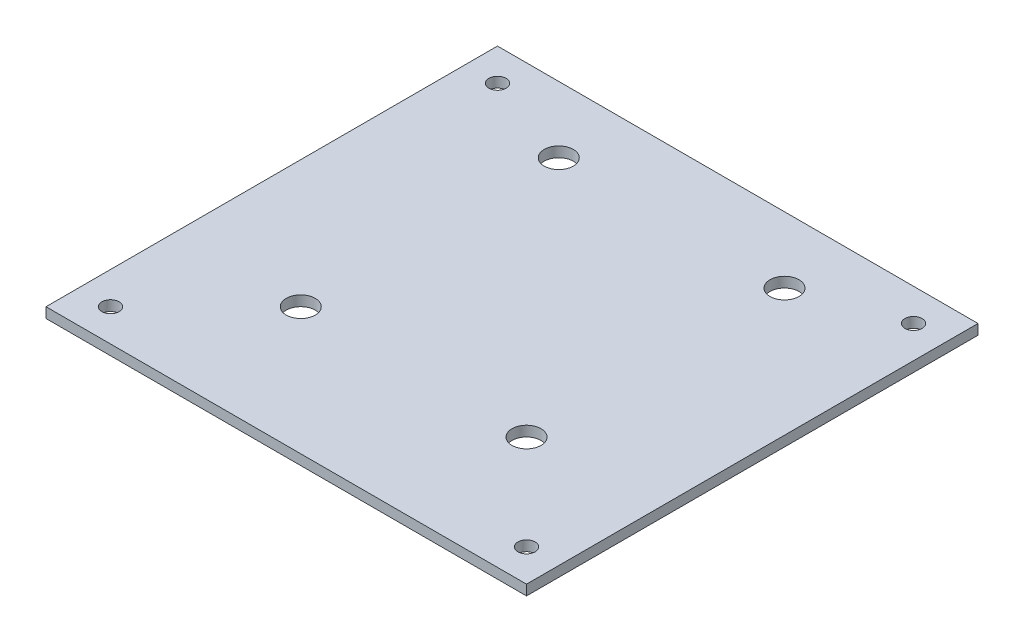
SolidWorks part; units mm, degrees
ref_plane "Front Plane" through (0, 0, 0) normal (0, 0, 1) x (1, 0, 0)
ref_plane "Top Plane" through (0, 0, 0) normal (0, 1, 0) x (1, 0, 0)
ref_plane "Right Plane" through (0, 0, 0) normal (1, 0, 0) x (0, 0, -1)
sketch "Sketch1" plane through (0, 0, 0) normal (0, 1, 0) x (1, 0, 0)
  line L1 (74.5, 70) -> (-74.5, 70)
  line L2 (74.5, 70) -> (74.5, -70)
  line L3 (74.5, -70) -> (-74.5, -70)
  line L4 (-74.5, 70) -> (-74.5, -70)
  line L5 (74.5, 70) -> (-74.5, -70) construction
  line L6 (74.5, -70) -> (-74.5, 70) construction
  point P0 (0, 0)
  dimension "D1" = 140
  dimension "D2" = 149
extrude "Boss-Extrude1" add sketch "Sketch1" along normal blind 3.175
sketch "Sketch2" plane through (0, 3.175, 0) normal (0, 1, 0) x (1, 0, 0)
  circle A0 centre (-35, 49.5) radius 4.5
  circle A1 centre (-35, -30.5) radius 4.5
  circle A2 centre (35, -30.5) radius 4.5
  circle A4 centre (35, 49.5) radius 4.5
extrude "Cut-Extrude1" cut sketch "Sketch2" against normal up to next
sketch "Sketch3" plane through (0, 3.175, 0) normal (0, 1, 0) x (-1, 0, 0)
  line L0 (64.5, -70) -> (64.5, 70) construction
  line L1 (-74.5, -70) -> (74.5, -70) construction
  line L2 (74.5, 70) -> (-74.5, 70) construction
  line L3 (74.5, 60) -> (-74.5, 60) construction
  line L4 (74.5, -70) -> (74.5, 70) construction
  line L5 (-74.5, 70) -> (-74.5, -70) construction
  line L6 (-64.5, -70) -> (-64.5, 70) construction
  circle A0 centre (64.5, 60) radius 2.665
  circle A1 centre (-64.5, 60) radius 2.665
  circle A2 centre (-64.5, -60) radius 2.665
  circle A3 centre (64.5, -60) radius 2.665
  dimension "D4" = 10
  dimension "D5" = 10
  dimension "D6" = 5.33
  dimension "D1" = 10
  dimension "D2" = 10
  dimension "D3" = 10
extrude "Cut-Extrude2" cut sketch "Sketch3" against normal up to next
